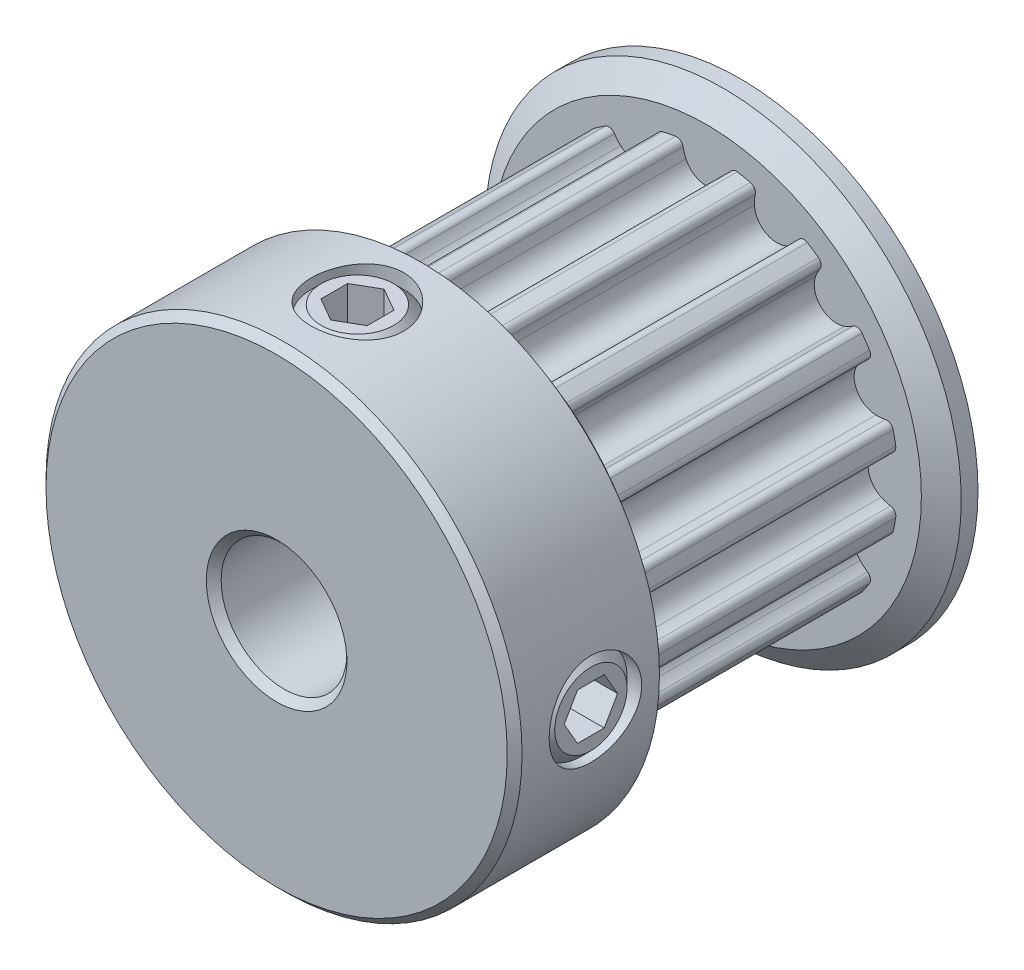
SolidWorks part; units mm, degrees
ref_plane "Front Plane" through (0, 0, 0) normal (0, 0, 1) x (1, 0, 0)
ref_plane "Top Plane" through (0, 0, 0) normal (0, 1, 0) x (1, 0, 0)
ref_plane "Right Plane" through (0, 0, 0) normal (1, 0, 0) x (0, 0, -1)
sketch "Sketch1" plane through (0, 0, 0) normal (0, 0, 1) x (1, 0, 0)
  line L1 (-2.553, 6.1245) -> (2.553, 6.1245) construction
  line L4 (0, 0) -> (0, 6.1245) construction
  line L5 (0, 6.1245) -> (0, 12.0677) construction
  line L6 (0, 7.6455) -> (2.9417, 7.0569) construction
  line L7 (2.9417, 7.0569) -> (3.8741, 6.6682) construction
  line L8 (2.9417, 7.0569) -> (2.553, 6.1245) construction
  line L9 (-2.9417, 7.0569) -> (-2.553, 6.1245) construction
  line L10 (-2.7951, 6.7052) -> (-3.7579, 9.015)
  line L11 (-3.7579, 9.015) -> (3.7579, 9.015)
  line L12 (3.7579, 9.015) -> (2.7951, 6.7052)
  circle A0 centre (0, 0) radius 7.6455 construction
  circle A1 centre (0, 0) radius 9.015 construction
  circle A2 centre (0, 0) radius 7.2645 construction
  arc A3 (-0.7739, 6.6229) -> (0.7739, 6.6229) centre (0, 6.9745) ccw
  arc A4 (-0.7739, 6.6229) -> (-0.8836, 6.9694) centre (0.61, 7.2516) cw
  arc A5 (-2.7951, 6.7052) -> (-1.1695, 7.1697) centre (0, 0) cw
  arc A6 (-0.8836, 6.9694) -> (-1.1695, 7.1697) centre (-1.1292, 6.923) ccw
  arc A7 (2.7951, 6.7052) -> (1.1695, 7.1697) centre (0, 0) ccw
  arc A8 (0.8836, 6.9694) -> (1.1695, 7.1697) centre (1.1292, 6.923) cw
  arc A9 (0.7739, 6.6229) -> (0.8836, 6.9694) centre (-0.61, 7.2516) ccw
  point P6 (0, 20.9083)
  point P11 (0, 7.6455)
  point P13 (0, 9.015)
  point P14 (0, 7.2645)
  dimension "D1" = 8.8406
  dimension "D2" = 4.4222
sketch "Sketch2" plane through (0, 0, 0) normal (1, 0, 0) x (0, 0, -1)
  line L0 (-8.775, 2.3812) -> (8.775, 2.3812)
  line L1 (-8.775, 2.3812) -> (-8.775, 9.015)
  line L2 (-3.29, 9.015) -> (-8.775, 9.015)
  line L3 (-3.925, 2.3813) -> (-3.925, 9.015) construction
  line L4 (-3.925, 9.015) -> (-2.655, 9.015) construction
  line L5 (-2.655, 9.015) -> (-2.655, 7.2645) construction
  line L6 (-2.655, 7.2645) -> (7.505, 7.2645)
  line L7 (7.505, 7.2645) -> (7.505, 9.015) construction
  line L8 (7.505, 9.015) -> (8.775, 9.015) construction
  line L9 (8.775, 9.015) -> (8.775, 2.3812)
  line L10 (-8.775, 0) -> (8.775, 0) construction
  line L11 (8.14, 9.015) -> (7.505, 8.1398)
  line L12 (-2.655, 8.1398) -> (-3.29, 9.015)
  line L14 (-2.655, 8.1398) -> (-2.655, 7.2645)
  line L15 (7.505, 7.2645) -> (7.505, 8.1398)
  line L16 (8.14, 9.015) -> (8.775, 9.015)
  arc A0 (-2.655, 8.1398) -> (-3.29, 9.015) centre (-3.5757, 8.1398) ccw construction
  arc A1 (7.505, 8.1398) -> (8.14, 9.015) centre (8.4257, 8.1398) cw construction
  point P12 (-2.655, 8.1398)
  point P14 (-3.29, 9.015)
  point P20 (7.505, 8.1398)
  point P21 (8.14, 9.015)
  point P25 (7.505, 0)
  point P26 (-2.655, 0)
  dimension "OA" = 17.55
  dimension "Bore" = 4.7625
  dimension "Outside Width" = 11.43
  dimension "Inside Width" = 10.16
revolve "Revolve1" add sketch "Sketch2" angle 360 mid plane about L10
sketch "Sketch3" plane through (0, 0, 0) normal (0, 0, 1) x (1, 0, 0)
  line L6 (3.7579, 9.015) -> (-3.7579, 9.015)
  line L7 (2.7951, 6.7052) -> (3.7579, 9.015)
  line L8 (-3.7579, 9.015) -> (-2.7951, 6.7052)
  line L9 (3.7579, 9.015) -> (-3.7579, 9.015)
  line L10 (2.7951, 6.7052) -> (3.7579, 9.015)
  line L11 (-3.7579, 9.015) -> (-2.7951, 6.7052)
  arc A8 (2.7951, 6.7052) -> (1.1695, 7.1697) centre (0, 0) ccw
  arc A9 (1.1695, 7.1697) -> (0.8836, 6.9694) centre (1.1292, 6.923) ccw
  arc A10 (0.7739, 6.6229) -> (0.8836, 6.9694) centre (-0.61, 7.2516) ccw
  arc A11 (-0.7739, 6.6229) -> (0.7739, 6.6229) centre (0, 6.9745) ccw
  arc A12 (-0.8836, 6.9694) -> (-0.7739, 6.6229) centre (0.61, 7.2516) ccw
  arc A13 (-0.8836, 6.9694) -> (-1.1695, 7.1697) centre (-1.1292, 6.923) ccw
  arc A14 (-1.1695, 7.1697) -> (-2.7951, 6.7052) centre (0, 0) ccw
  arc A15 (2.7951, 6.7052) -> (1.1695, 7.1697) centre (0, 0) ccw
  arc A16 (1.1695, 7.1697) -> (0.8836, 6.9694) centre (1.1292, 6.923) ccw
  arc A17 (0.7739, 6.6229) -> (0.8836, 6.9694) centre (-0.61, 7.2516) ccw
  arc A18 (-0.7739, 6.6229) -> (0.7739, 6.6229) centre (0, 6.9745) ccw
  arc A19 (-0.8836, 6.9694) -> (-0.7739, 6.6229) centre (0.61, 7.2516) ccw
  arc A20 (-0.8836, 6.9694) -> (-1.1695, 7.1697) centre (-1.1292, 6.923) ccw
  arc A21 (-1.1695, 7.1697) -> (-2.7951, 6.7052) centre (0, 0) ccw
  dimension "D1" = 0
extrude "Cut-Extrude1" cut sketch "Sketch3" against normal up to vertex (7.505 mm away) from vertex up to point (0, 7.2645, -7.505) starting at point (0, 7.2645, 2.655)
pattern_circular "CirPattern1" count 16 over 360 about axis through (0, 0, 8.775) along (0, 0, 1) of "Cut-Extrude1"
sketch "Sketch4" plane through (0, 0, 0) normal (1, 0, 0) x (0, -1, 0)
  line L0 (0, -2.655) -> (0, -8.775) construction
  line L1 (-2.3812, -8.775) -> (2.3812, -8.775) construction
  line L2 (8.1398, -2.655) -> (-8.1398, -2.655) construction
  circle A0 centre (0, -5.715) radius 1.7526
extrude "Cut-Extrude2" cut sketch "Sketch4" along normal through all
ref_plane "Plane1" through (0, 0, 5.715) normal (0, 0, 1) x (1, 0, 0)
sketch "Sketch5" plane through (0, 0, 5.715) normal (0, 0, 1) x (1, 0, 0)
  line L0 (0, 0) -> (0, 9.015) construction
  line L1 (2.3812, -1.3716) -> (2.3812, 0)
  line L2 (2.7622, -1.7526) -> (8.462, -1.7526)
  line L3 (2.3812, 0) -> (9.015, 0) construction
  line L4 (2.3812, 0) -> (8.843, 0)
  line L5 (8.843, 0) -> (8.843, -1.3716)
  line L6 (2.7622, -1.7526) -> (2.3812, -1.3716)
  line L7 (8.843, -1.3716) -> (8.462, -1.7526)
  circle A0 centre (0, 0) radius 9.015 construction
  circle A1 centre (0, 0) radius 2.3812 construction
  point P2 (2.3812, -1.7526)
  point P11 (8.843, -1.7526)
revolve "Revolve2" add sketch "Sketch5" angle 360 mid plane about L4
sketch "Sketch6" plane through (8.843, 5.3841, 0) normal (-1, 0, 0) x (0, -1, 0)
  line L1 (5.3841, 6.7269) -> (4.5078, 6.2209)
  line L2 (4.5078, 6.2209) -> (4.5078, 5.2091)
  line L3 (4.5078, 5.2091) -> (5.3841, 4.7031)
  line L4 (5.3841, 4.7031) -> (6.2604, 5.2091)
  line L5 (6.2604, 5.2091) -> (6.2604, 6.2209)
  line L6 (6.2604, 6.2209) -> (5.3841, 6.7269)
  circle A0 centre (5.3841, 5.715) radius 0.8763 construction
  dimension "D1" = 1.7526
extrude "Cut-Extrude3" cut sketch "Sketch6" along normal blind 1.3144
pattern_circular "CirPattern3" count 2 over 90 about axis through (0, 0, 8.775) along (0, 0, 1) of "Cut-Extrude2", "Revolve2", "Cut-Extrude3"
chamfer "Chamfer1" distance 0.2807 angle 45 2 edges at (2.3812, 0, 8.775) (9.015, 0, 8.775)
ref_axis "Center Axis 1" through (0, 0, -8.775) along (0, 0, 1)
ref_plane "Contact Plane 1" through (0, 0, 8.775) normal (0, 0, 1) x (1, 0, 0)
ref_plane "Contact Plane 2" through (0, 0, -8.775) normal (0, 0, -1) x (-1, 0, 0)
equation "\"D2@Sketch1\"= \"D1@Sketch1\" / 2"
equation "\"D1@Sketch6\" = \"Set Screw@Sketch4\" / 2"
equation "\"D1@Cut-Extrude3\" = \"D1@Sketch6\"*.75"
